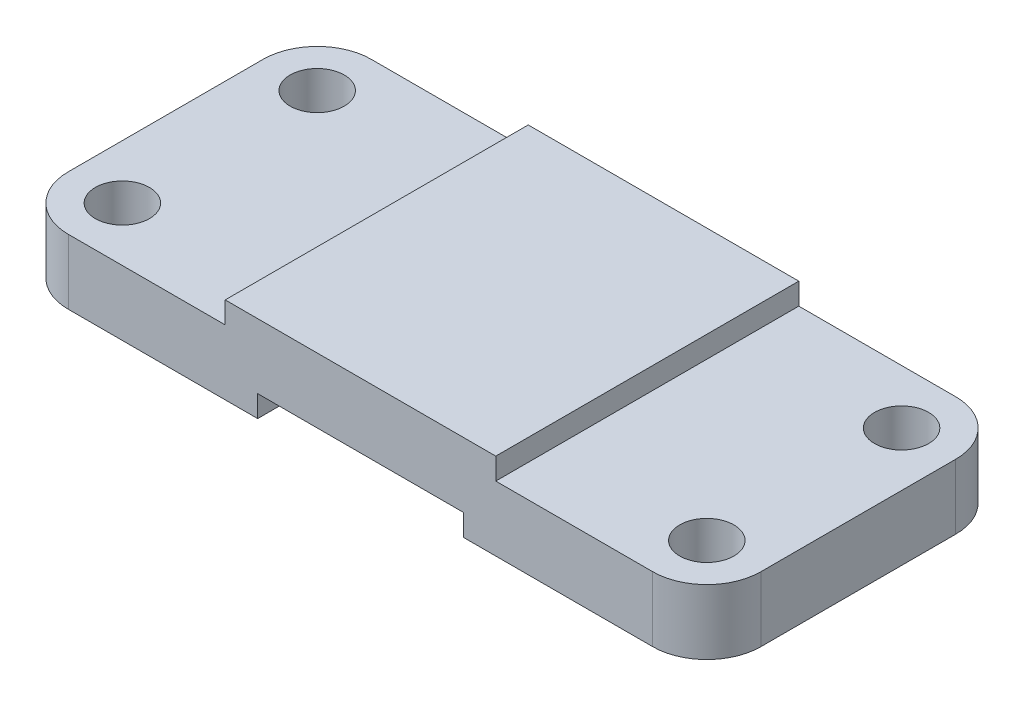
SolidWorks part; units mm, degrees
ref_plane "Ön Düzlem" through (0, 0, 0) normal (0, 0, 1) x (1, 0, 0)
ref_plane "Üst Düzlem" through (0, 0, 0) normal (0, 1, 0) x (1, 0, 0)
ref_plane "Sağ Düzlem" through (0, 0, 0) normal (1, 0, 0) x (0, 0, -1)
sketch "Çizim1" plane through (0, 0, 0) normal (0, 1, 0) x (1, 0, 0)
  line L0 (-50, 56) -> (-89, 56)
  line L1 (0, 0) -> (-50, 0)
  line L2 (0, 0) -> (0, 56)
  line L3 (0, 56) -> (-50, 56)
  line L4 (-50, 0) -> (-50, 56)
  line L5 (-89, 56) -> (-89, 0)
  line L6 (-89, 0) -> (-50, 0)
  line L7 (0, 0) -> (39, 0)
  line L8 (39, 0) -> (39, 56)
  line L9 (39, 56) -> (0, 56)
  line L10 (-79, 56) -> (-79, -13.6882) construction
  line L11 (29, 56) -> (29, -10.9827) construction
  dimension "D1" = 50
  dimension "D2" = 56
  dimension "D3" = 128
  dimension "D4" = 108
  dimension "D5" = 29
  dimension "D6" = 10
extrude "Yükseklik-Ekstrüzyon1" add sketch "Çizim1" along normal blind 16 contours L4 L1 L2 L3 region at (-25, 0, -28)
extrude "Yükseklik-Ekstrüzyon2" add sketch "Çizim1<3>" along normal blind 12 contours L5 L6 L4 L0 | L8 L9 L2 L7 region at (-69.5, 0, -28) region at (19.5, 0, -28)
sketch "Çizim1<3>" plane through (0, 0, 0) normal (0, 1, 0) x (1, 0, 0) same geometry as "Çizim1"
fillet "Radyus1" radius 10 4 edges at (39, 6, 0) (39, 6, -56) (-89, 6, -56) (-89, 6, 0)
sketch "Çizim2" plane through (0, 12, 0) normal (0, 1, 0) x (1, 0, 0)
  circle A0 centre (-79, 46) radius 5
  circle A1 centre (-79, 10) radius 5
  arc A8 (-79, 56) -> (-89, 46) centre (-79, 46) ccw construction
  arc A9 (-89, 10) -> (-79, 0) centre (-79, 10) ccw construction
  dimension "D1" = 10
  dimension "D2" = 10
extrude "Kes-Ekstrüzyon1" cut sketch "Çizim2" against normal through all
sketch "Çizim3" plane through (0, 12, 0) normal (0, 1, 0) x (1, 0, 0)
  circle A0 centre (29, 46) radius 5
  circle A1 centre (29, 10) radius 5
  arc A2 (39, 46) -> (29, 56) centre (29, 46) ccw construction
  arc A3 (29, 0) -> (39, 10) centre (29, 10) ccw construction
  dimension "D1" = 10
  dimension "D2" = 10
extrude "Kes-Ekstrüzyon2" cut sketch "Çizim3" against normal through all
sketch "Çizim4" plane through (0, 0, 0) normal (0, 0, 1) x (1, 0, 0)
  line L0 (-44, 0) -> (-44, 4)
  line L1 (29, 0) -> (-79, 0) construction
  line L2 (-44, 4) -> (-6, 4)
  line L3 (-6, 4) -> (-6, 0)
  line L5 (-50, 16) -> (-50, 12) construction
  line L6 (-44, 0) -> (-6, 0)
  dimension "D1" = 4
  dimension "D2" = 38
  dimension "D3" = 6
extrude "Kes-Ekstrüzyon4" cut sketch "Çizim4" against normal through all
